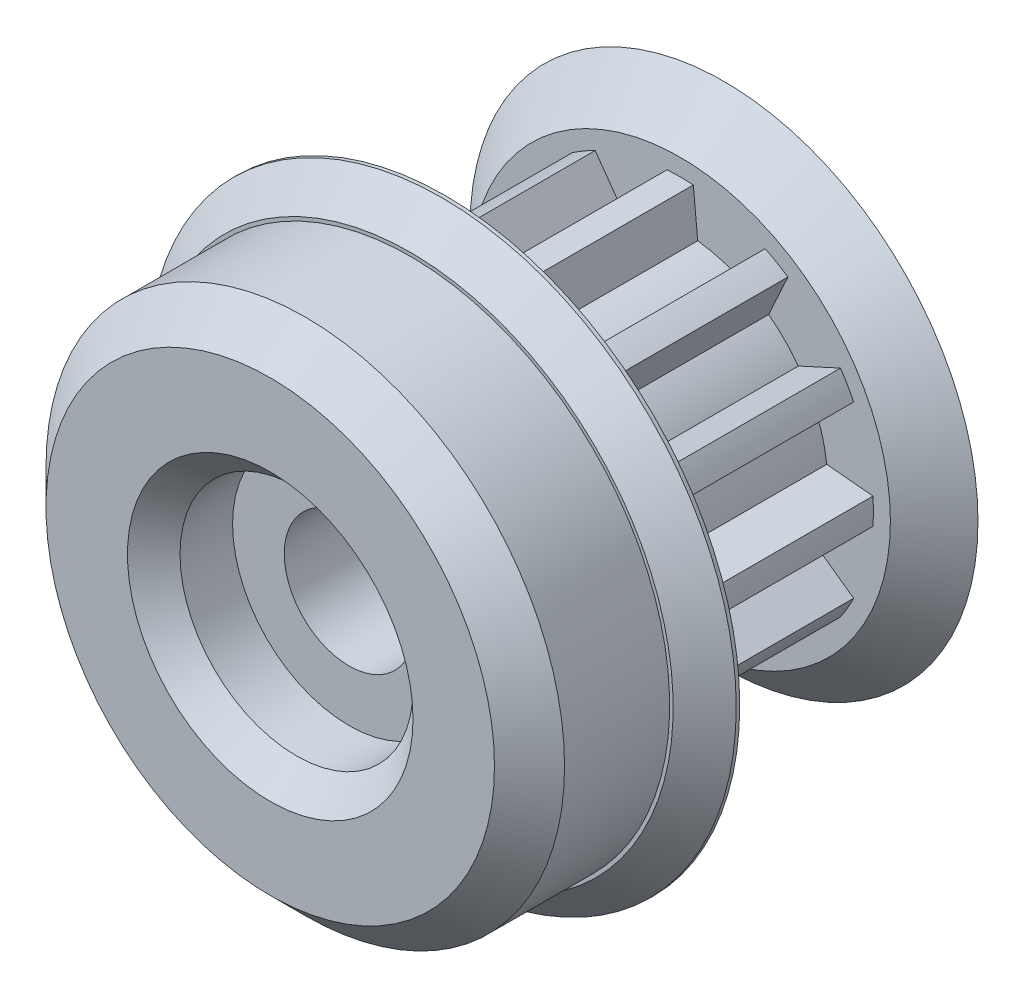
SolidWorks part; units mm, degrees
material "ABS"
ref_plane "Alzado" through (0, 0, 0) normal (0, 0, 1) x (1, 0, 0)
ref_plane "Planta" through (0, 0, 0) normal (0, 1, 0) x (1, 0, 0)
ref_plane "Vista lateral" through (0, 0, 0) normal (1, 0, 0) x (0, 0, -1)
sketch "Croquis1" plane through (0, 0, 0) normal (0, 0, 1) x (1, 0, 0)
  line L0 (0, 0) -> (0, 4.6049) construction
  line L1 (0.375, 5.5012) -> (0.5, 4.1842)
  line L2 (-0.375, 5.5012) -> (-0.5, 4.1842)
  line L3 (2.4259, 4.9517) -> (1.6591, 3.8737)
  line L4 (3.0754, 4.5767) -> (2.5251, 3.3737)
  line L5 (4.5767, 3.0754) -> (3.3737, 2.5251)
  line L6 (4.9517, 2.4259) -> (3.8737, 1.6591)
  line L7 (5.5012, 0.375) -> (4.1842, 0.5)
  line L8 (5.5012, -0.375) -> (4.1842, -0.5)
  line L9 (4.9517, -2.4259) -> (3.8737, -1.6591)
  line L10 (4.5767, -3.0754) -> (3.3737, -2.5251)
  line L11 (3.0754, -4.5767) -> (2.5251, -3.3737)
  line L12 (2.4259, -4.9517) -> (1.6591, -3.8737)
  line L13 (0.375, -5.5012) -> (0.5, -4.1842)
  line L14 (-0.375, -5.5012) -> (-0.5, -4.1842)
  line L15 (-2.4259, -4.9517) -> (-1.6591, -3.8737)
  line L16 (-3.0754, -4.5767) -> (-2.5251, -3.3737)
  line L17 (-4.5767, -3.0754) -> (-3.3737, -2.5251)
  line L18 (-4.9517, -2.4259) -> (-3.8737, -1.6591)
  line L19 (-5.5012, -0.375) -> (-4.1842, -0.5)
  line L20 (-5.5012, 0.375) -> (-4.1842, 0.5)
  line L21 (-4.9517, 2.4259) -> (-3.8737, 1.6591)
  line L22 (-4.5767, 3.0754) -> (-3.3737, 2.5251)
  line L23 (-3.0754, 4.5767) -> (-2.5251, 3.3737)
  line L24 (-2.4259, 4.9517) -> (-1.6591, 3.8737)
  circle A0 centre (0, 0) radius 1.85
  arc A1 (1.6591, 3.8737) -> (0.5, 4.1842) centre (0, 0) ccw
  arc A2 (3.0754, 4.5767) -> (2.4259, 4.9517) centre (0, 0) ccw
  arc A3 (4.9517, 2.4259) -> (4.5767, 3.0754) centre (0, 0) ccw
  arc A4 (5.5012, -0.375) -> (5.5012, 0.375) centre (0, 0) ccw
  arc A5 (4.5767, -3.0754) -> (4.9517, -2.4259) centre (0, 0) ccw
  arc A6 (2.4259, -4.9517) -> (3.0754, -4.5767) centre (0, 0) ccw
  arc A7 (-0.375, -5.5012) -> (0.375, -5.5012) centre (0, 0) ccw
  arc A8 (-3.0754, -4.5767) -> (-2.4259, -4.9517) centre (0, 0) ccw
  arc A9 (-4.9517, -2.4259) -> (-4.5767, -3.0754) centre (0, 0) ccw
  arc A10 (-5.5012, 0.375) -> (-5.5012, -0.375) centre (0, 0) ccw
  arc A11 (-4.5767, 3.0754) -> (-4.9517, 2.4259) centre (0, 0) ccw
  arc A12 (-2.4259, 4.9517) -> (-3.0754, 4.5767) centre (0, 0) ccw
  arc A13 (0.375, 5.5012) -> (-0.375, 5.5012) centre (0, 0) ccw
  arc A14 (3.3737, 2.5251) -> (2.5251, 3.3737) centre (0, 0) ccw
  arc A15 (4.1842, 0.5) -> (3.8737, 1.6591) centre (0, 0) ccw
  arc A16 (3.8737, -1.6591) -> (4.1842, -0.5) centre (0, 0) ccw
  arc A17 (2.5251, -3.3737) -> (3.3737, -2.5251) centre (0, 0) ccw
  arc A18 (0.5, -4.1842) -> (1.6591, -3.8737) centre (0, 0) ccw
  arc A19 (-1.6591, -3.8737) -> (-0.5, -4.1842) centre (0, 0) ccw
  arc A20 (-3.3737, -2.5251) -> (-2.5251, -3.3737) centre (0, 0) ccw
  arc A21 (-4.1842, -0.5) -> (-3.8737, -1.6591) centre (0, 0) ccw
  arc A22 (-3.8737, 1.6591) -> (-4.1842, 0.5) centre (0, 0) ccw
  arc A23 (-2.5251, 3.3737) -> (-3.3737, 2.5251) centre (0, 0) ccw
  arc A24 (-0.5, 4.1842) -> (-1.6591, 3.8737) centre (0, 0) ccw
  dimension "D1" = 1
  dimension "D2" = 3.7
  dimension "D4" = 1.3
  dimension "D3" = 0.75
  dimension "D6" = 1.2
  dimension "D5" = 12
extrude "Saliente-Extruir1" add sketch "Croquis1" along normal blind 6.7
sketch "Croquis2" plane through (0, 0, 6.7) normal (0, 0, 1) x (1, 0, 0)
  circle A0 centre (0, 0) radius 3.325
  circle A1 centre (0, 0) radius 7.4
  dimension "D1" = 14.8
  dimension "D2" = 6.65
extrude "Saliente-Extruir2" add sketch "Croquis2" along normal blind 5
chamfer "Chaflán1" distance 1 angle 45 1 edges at (7.4, 0, 11.7)
sketch "Croquis3" plane through (0, 0, 0) normal (0, 0, -1) x (-1, 0, 0)
  circle A0 centre (0, 0) radius 1.85
  circle A1 centre (0, 0) radius 7.5
  circle A2 centre (0, 0) radius 1.85 construction
  dimension "D1" = 15
extrude "Saliente-Extruir3" add sketch "Croquis3" along normal blind 1.25
chamfer "Chaflán2" distance 0.75 angle 45 1 edges at (3.325, 0, 11.7)
sketch "Croquis4" plane through (0, 0, 6.7) normal (0, 0, 1) x (1, 0, 0)
  circle A0 centre (0, 0) radius 1.85
  circle A1 centre (0, 0) radius 4.8926
  circle A2 centre (0, 0) radius 1.85 construction
extrude "Saliente-Extruir4" add sketch "Croquis4" along normal blind 2.75
chamfer "Chaflán3" distance 1 angle 45 12 edges at (4.0704, 1.0907, 6.7) (2.9798, 2.9798, 6.7) (1.0907, 4.0704, 6.7) (-1.0907, 4.0704, 6.7) (-2.9798, 2.9798, 6.7) (-4.0704, -1.0907, 6.7) (-4.0704, 1.0907, 6.7) (-2.9798, -2.9798, 6.7) (-1.0907, -4.0704, 6.7) (1.0907, -4.0704, 6.7) (2.9798, -2.9798, 6.7) (4.0704, -1.0907, 6.7)
chamfer "Chaflán4" distance 1.5 angle 45 1 edges at (-7.5, 0, 0)
sketch "Croquis6" plane through (0, 0, 6.7) normal (0, 0, -1) x (-1, 0, 0)
  circle A0 centre (0, 0) radius 8.4
  circle A1 centre (0, 0) radius 7.4 construction
  circle A2 centre (0, 0) radius 1.85
  circle A3 centre (0, 0) radius 1.85 construction
  dimension "D1" = 1
extrude "Saliente-Extruir5" add sketch "Croquis6" against normal blind 1
chamfer "Chaflán5" distance 0.9 angle 45 1 edges at (-8.4, 0, 7.7)
sketch "Croquis8" plane through (0, 0, -1.25) normal (0, 0, -1) x (-1, 0, 0)
  line L1 (-2.2258, -3.5176) -> (1.9334, -3.6864)
  line L2 (1.9334, -3.6864) -> (4.1592, -0.1688)
  line L3 (4.1592, -0.1688) -> (2.2258, 3.5176)
  line L4 (2.2258, 3.5176) -> (-1.9334, 3.6864)
  line L5 (-1.9334, 3.6864) -> (-4.1592, 0.1688)
  line L6 (-4.1592, 0.1688) -> (-2.2258, -3.5176)
  circle A0 centre (0, 0) radius 3.6049 construction
extrude "Cortar-Extruir1" cut sketch "Croquis8" against normal blind 8
chamfer "Chaflán6" distance 1 angle 45 6 edges at (-0.1462, 3.602, -1.25) (3.0463, 1.9276, -1.25) (3.1925, -1.6744, -1.25) (0.1462, -3.602, -1.25) (-3.0463, -1.9276, -1.25) (-3.1925, 1.6744, -1.25)
